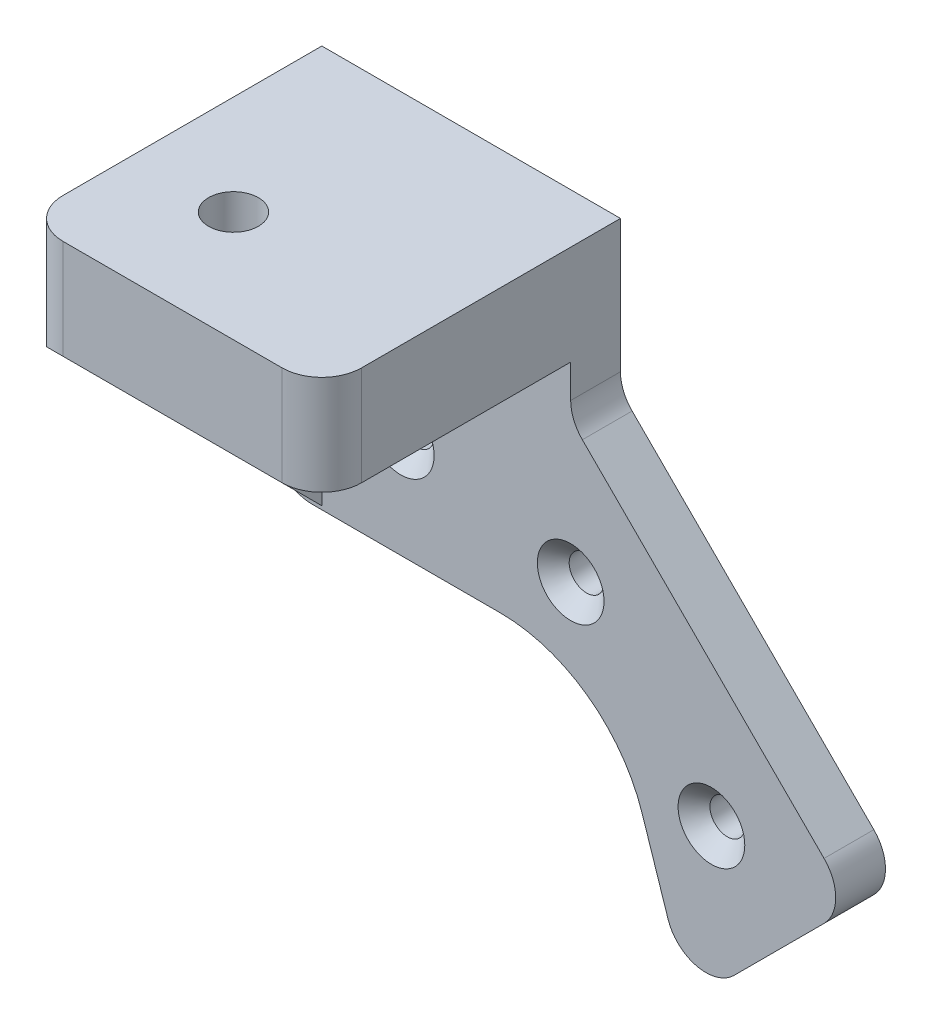
SolidWorks part; units mm, degrees
ref_plane "Front Plane" through (0, 0, 0) normal (0, 0, 1) x (1, 0, 0)
ref_plane "Top Plane" through (0, 0, 0) normal (0, 1, 0) x (1, 0, 0)
ref_plane "Right Plane" through (0, 0, 0) normal (1, 0, 0) x (0, 0, -1)
sketch "Sketch1" plane through (0, 0, 0) normal (0, 0, 1) x (1, 0, 0)
  line L0 (15, 27.5) -> (15, 12.5)
  line L5 (-15, 27.5) -> (15, 27.5)
  line L6 (-15, 27.5) -> (-15, -27.5)
  line L7 (-15, -27.5) -> (15, -27.5)
  line L9 (15, 12.5) -> (43.2843, -15.7843)
  line L10 (-15, -27.5) -> (15, 27.5) construction
  line L11 (43.2843, -15.7843) -> (23.2843, -35.7843)
  line L12 (23.2843, -35.7843) -> (15, -27.5)
  point P0 (0, 0)
  dimension "D1" = 45
  dimension "D2" = 55
  dimension "D3" = 30
  dimension "D4" = 40
  dimension "D5" = 15
extrude "Boss-Extrude1" add sketch "Sketch1" along normal blind 5
sketch "Sketch3" plane through (0, 0, 5) normal (0, 0, 1) x (1, 0, 0)
  line L0 (15, 12.5) -> (15, 27.5) construction
  line L1 (-15, 27.5) -> (15, 27.5)
  line L2 (-15, 27.5) -> (-15, 17.5)
  line L3 (-15, 17.5) -> (15, 17.5)
  line L4 (15, 27.5) -> (15, 17.5)
  dimension "D1" = 10
extrude "Boss-Extrude2" add sketch "Sketch3" along normal blind 25
sketch "Sketch4" plane through (0, 27.5, 0) normal (0, 1, 0) x (1, 0, 0)
  line L0 (-15, -30) -> (-15, 0) construction
  line L1 (15, -30) -> (-15, -30) construction
  line L2 (15, -30) -> (15, -5) construction
  line L3 (15, -5) -> (-15, -5) construction
  line L4 (-15, -30) -> (-15, -5) construction
  line L5 (15, -30) -> (15, 0) construction
  line L6 (-15, 0) -> (15, 0) construction
  line L7 (-15, 0) -> (-15, 5) construction
  line L8 (-15, 5) -> (15, 5) construction
  line L9 (15, 0) -> (15, 5) construction
  circle A0 centre (-5, -18.88) radius 2.5
  circle A1 centre (-5, -18.88) radius 6.5 construction
  dimension "D3" = 13
  dimension "D4" = 5
  dimension "D1" = 25
  dimension "D2" = 5
  dimension "D5" = 23.88
  dimension "D6" = 20
extrude "Cut-Extrude1" cut sketch "Sketch4" against normal through all
sketch "Sketch6" plane through (-15, 0, 0) normal (-1, 0, 0) x (0, 0, 1)
  line L0 (30, 17.5) -> (5, -7.5)
  line L1 (5, 17.5) -> (5, -27.5) construction
  dimension "D1" = 45
rib "Rib1" sketch "Sketch6" sketch "Sketch6" thickness 5 extrusion direction parallel to sketch draft on no parameters "D1"=5
sketch "Sketch7" plane through (0, 0, 5) normal (0, 0, 1) x (1, 0, 0)
  line L0 (22.1747, -18.1589) -> (26.8198, -32.2487)
  line L1 (-15, -7.8553) -> (7.9289, -7.8553)
  line L2 (-15, -7.8553) -> (-15, -27.5)
  line L3 (-15, -7.5) -> (-15, -27.5) construction
  line L4 (-15, -27.5) -> (15, -27.5) construction
  line L5 (15, 27.5) -> (-15, 27.5) construction
  line L6 (23.2843, -35.7843) -> (43.2843, -15.7843) construction
  line L7 (-15, -27.5) -> (23.2843, -35.7843)
  line L8 (23.2843, -35.7843) -> (26.8198, -32.2487)
  arc A0 (22.1747, -18.1589) -> (7.9289, -7.8553) centre (7.9289, -22.8553) ccw
  circle A1 centre (7.9289, -22.8553) radius 14 construction
  dimension "D1" = 1
  dimension "D2" = 5
extrude "Cut-Extrude2" cut sketch "Sketch7" against normal up to vertex (5 mm away) up to point (-15, -27.5, 0)
sketch "Sketch8" plane through (0, 17.5, 0) normal (0, -1, 0) x (-1, 0, 0)
  line L1 (0.2657, -18.88) -> (2.6329, -22.98)
  line L2 (2.6329, -22.98) -> (7.3671, -22.98)
  line L3 (7.3671, -22.98) -> (9.7343, -18.88)
  line L4 (9.7343, -18.88) -> (7.3671, -14.78)
  line L5 (7.3671, -14.78) -> (2.6329, -14.78)
  line L6 (2.6329, -14.78) -> (0.2657, -18.88)
  circle A0 centre (5, -18.88) radius 4.1 construction
  dimension "D1" = 8.2
extrude "Cut-Extrude3" cut sketch "Sketch8" against normal blind 5
fillet "Fillet1" radius 4 2 edges at (-15, 22.5, 30) (15, 22.5, 30)
sketch "Sketch9" plane through (0, 0, 5) normal (0, 0, 1) x (1, 0, 0)
  line L0 (15, -1.6421) -> (22.0711, 5.4289) construction
  line L1 (43.2843, -15.7843) -> (15, 12.5) construction
  line L2 (29.1421, -15.7843) -> (36.2132, -8.7132) construction
  line L3 (26.8198, -32.2487) -> (43.2843, -15.7843) construction
  line L4 (15, 12.5) -> (-5.3553, -7.8553) construction
  line L5 (7.9289, -7.8553) -> (-15, -7.8553) construction
  line L6 (15, 12.5) -> (-15, 12.5) construction
  line L7 (-15, 13.5) -> (-15, -7.5) construction
  circle A0 centre (15, -1.6421) radius 1.75
  circle A1 centre (29.1421, -15.7843) radius 1.75
  circle A2 centre (-2.0711, 2.5) radius 1.75
  dimension "D1" = 3.5
  dimension "D5" = 5
  dimension "D2" = 10
  dimension "D3" = 10
  dimension "D4" = 20
  dimension "D6" = 10
extrude "Cut-Extrude4" cut sketch "Sketch9" against normal through all
chamfer "Chamfer1" distance 1.6 angle 45 3 edges at (30.8921, -15.7843, 5) (16.75, -1.6421, 5) (-0.3211, 2.5, 5)
fillet "Fillet2" radius 4 4 edges at (15, 12.5, 2.5) (43.2843, -15.7843, 2.5) (26.8198, -32.2487, 2.5) (-15, -7.8553, 2.5)
